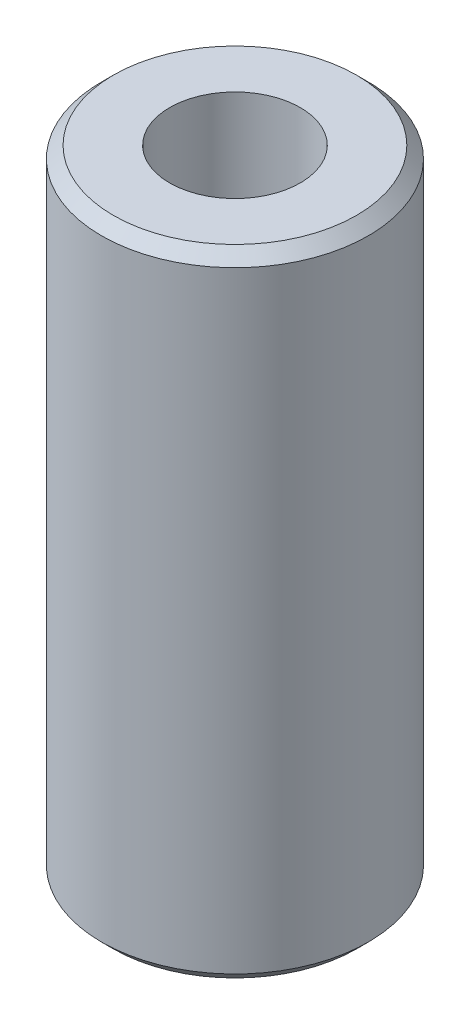
SolidWorks part; units mm, degrees
ref_plane "Front Plane" through (0, 0, 0) normal (0, 0, 1) x (1, 0, 0)
ref_plane "Top Plane" through (0, 0, 0) normal (0, 1, 0) x (1, 0, 0)
ref_plane "Right Plane" through (0, 0, 0) normal (1, 0, 0) x (0, 0, -1)
sketch "Sketch1" plane through (0, 0, 0) normal (0, 1, 0) x (1, 0, 0)
  circle A0 centre (0, 0) radius 45
  dimension "SHAFT_OD" = 90
extrude "Boss-Extrude1" add sketch "Sketch1" along normal blind 214.3677
sketch "Sketch2" plane through (0, 0, 0) normal (0, 1, 0) x (1, 0, 0)
  circle A0 centre (0, 0) radius 22.0454
  dimension "BORE_D" = 44.0908
extrude "Cut-Extrude1" cut sketch "Sketch2" along normal through all
chamfer "Chamfer1" distance 3.9756 angle 45 2 edges at (0, 214.3677, 45) (0, 0, 45)
